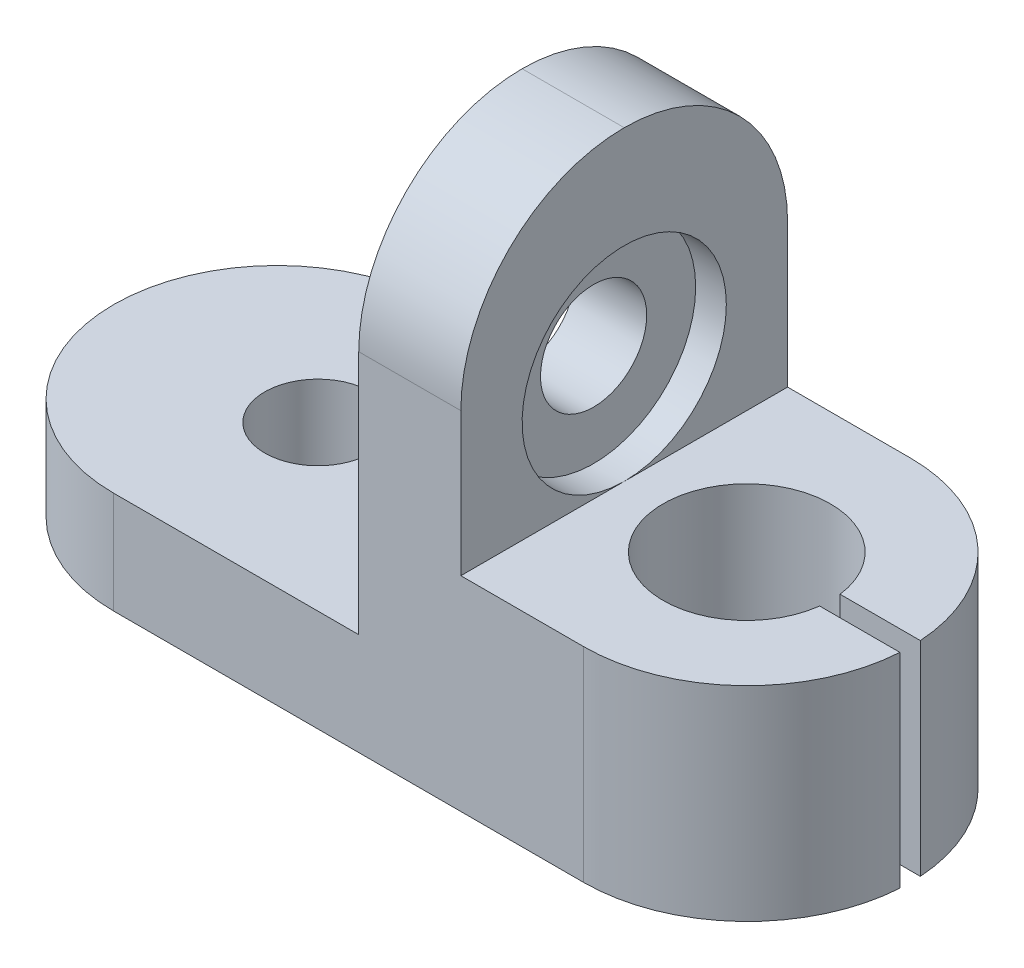
SolidWorks part; units mm, degrees
material "PET"
ref_plane "Front Plane" through (0, 0, 0) normal (0, 0, 1) x (1, 0, 0)
ref_plane "Top Plane" through (0, 0, 0) normal (0, 1, 0) x (1, 0, 0)
ref_plane "Right Plane" through (0, 0, 0) normal (1, 0, 0) x (0, 0, -1)
sketch "Sketch1" plane through (0, 0, 0) normal (0, 1, 0) x (1, 0, 0)
  line L0 (-25, 0) -> (14, 0) construction
  line L1 (-25, 8) -> (14, 8)
  line L2 (-25, 8) -> (-25, -8)
  line L3 (-25, -8) -> (14, -8)
  line L4 (14, 8) -> (14, -8)
  line L5 (-5, 8) -> (-5, -8)
  line L6 (-25, 8) -> (-5, 8) construction
  line L7 (-15, 8) -> (-15, -8) construction
  line L8 (0, 8) -> (0, -8)
  line L9 (9.9686, 0) -> (15.975, 0) construction
  line L10 (14, -0.5) -> (10.0694, -0.5)
  line L11 (14, -0.5) -> (14, 0.5)
  line L12 (14, 0.5) -> (10.0694, 0.5)
  line L13 (12.0347, 0.5) -> (12.0347, -0.5) construction
  arc A0 (10.0694, 0.5) -> (10.0694, -0.5) centre (6, 0) ccw
  circle A1 centre (-15, 0) radius 2.6
  dimension "D1" = 20
  dimension "D5" = 5.2
  dimension "D6" = 8.2
  dimension "D11" = 8
  dimension "D2" = 0
  dimension "D3" = 0
  dimension "D4" = 0
  dimension "D7" = 16
  dimension "D8" = 0
  dimension "D9" = 5
  dimension "D10" = 0
  dimension "D12" = 6
  dimension "D13" = 90
  dimension "D14" = 1
extrude "Boss-Extrude2" add sketch "Sketch1" along normal blind 5 contours L5 L1 L2 L3 A1 | L8 L1 L5 L3 | L1 L8 L3 L4 A0 region at (-15, 0, -7.7439) region at (-2.5, 0, 0) region at (7, 0, -7.7874)
extrude "Boss-Extrude3" add sketch "Sketch1<4>" along normal blind 10 contours L1 L8 L3 L4 A0 region at (7, 0, -7.7874)
sketch "Sketch1<4>" plane through (0, 0, 0) normal (0, 1, 0) x (1, 0, 0) same geometry as "Sketch1"
extrude "Boss-Extrude4" add sketch "Sketch1<5>" along normal blind 25 contours L8 L1 L5 L3 region at (-2.5, 0, 0)
sketch "Sketch1<5>" plane through (0, 0, 0) normal (0, 1, 0) x (1, 0, 0) same geometry as "Sketch1"
fillet "Fillet1" radius 8 1 edges at (14, 5, 8)
fillet "Fillet2" radius 8 1 edges at (14, 5, -8)
fillet "Fillet3" radius 8 1 edges at (-25, 2.5, 8)
fillet "Fillet4" radius 8 1 edges at (-25, 2.5, -8)
fillet "Fillet5" radius 8 1 edges at (-2.5, 25, 8)
fillet "Fillet6" radius 8 1 edges at (-2.5, 25, -8)
sketch "Sketch3" plane through (-5, 0, 0) normal (-1, 0, 0) x (0, 0, 1)
  line L0 (0, 25) -> (0, 5) construction
  circle A0 centre (0, 15) radius 2.6
  point P7 (0, 15)
  dimension "D1" = 5.2
  dimension "D2" = 0
  dimension "D3" = 0
extrude "Cut-Extrude1" cut sketch "Sketch3" against normal blind 25 contours A0
sketch "Sketch4" plane through (0, 0, 0) normal (1, 0, 0) x (0, 0, -1)
  circle A0 centre (0, 15) radius 5
  dimension "D1" = 10
extrude "Cut-Extrude2" cut sketch "Sketch4" against normal blind 1.5
